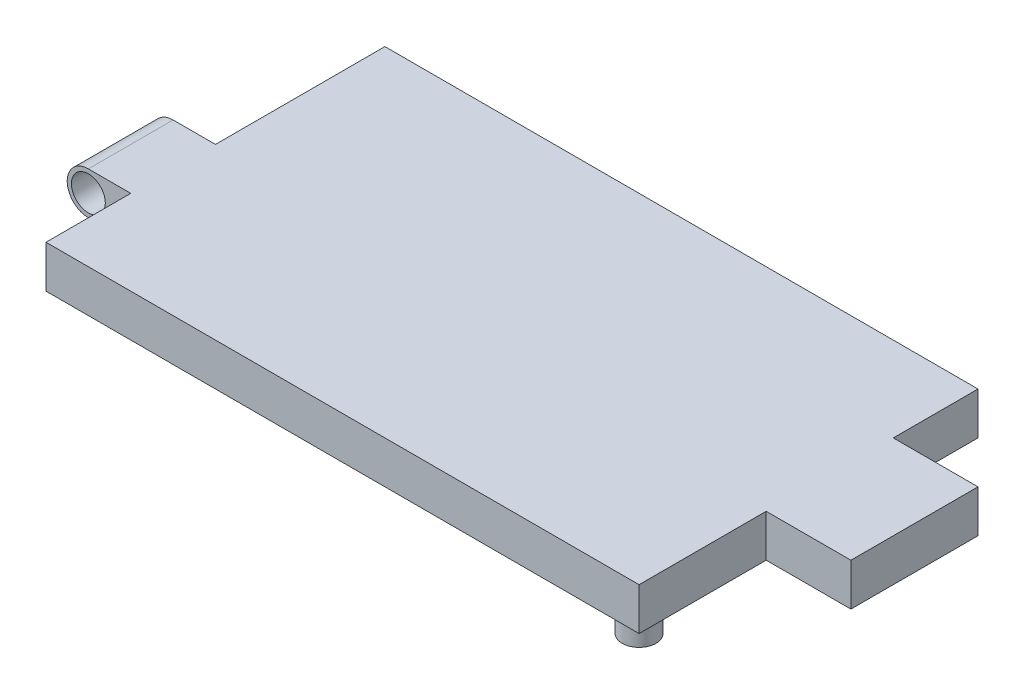
SolidWorks part; units mm, degrees
ref_plane "Plan de face" through (0, 0, 0) normal (0, 0, 1) x (1, 0, 0)
ref_plane "Plan de dessus" through (0, 0, 0) normal (0, 1, 0) x (1, 0, 0)
ref_plane "Plan de droite" through (0, 0, 0) normal (1, 0, 0) x (0, 0, -1)
sketch "Esquisse1" plane through (0, 0, 0) normal (0, 0, 1) x (1, 0, 0)
  line L0 (-80, 33.1442) -> (-80, -29.1403) construction
  line L5 (82.5, 15) -> (-82.5, -15) construction
  line L6 (82.5, -15) -> (-82.5, 15) construction
  line L7 (-88.7967, 0) -> (66.0295, 0) construction
  line L8 (-80, 2.5) -> (0, 2.5)
  line L9 (0, 2.5) -> (0, -2.5)
  line L10 (0, -2.5) -> (-80, -2.5)
  circle A0 centre (-80, 0) radius 2
  arc A1 (-80, 2.5) -> (-80, -2.5) centre (-80, 0) ccw
  point P0 (0, 0)
  dimension "D4" = 4
  dimension "D1" = 165
  dimension "D2" = 30
  dimension "D3" = 80
extrude "BASE" add sketch "Esquisse1" along normal blind 5 and the other way blind 5
sketch "Esquisse2" plane through (0, 0, 5) normal (0, 0, 1) x (1, 0, 0)
  line L0 (-75, 2.5) -> (-75, -2.5)
  line L1 (0, 2.5) -> (-80, 2.5) construction
  line L2 (-80, -2.5) -> (0, -2.5) construction
  line L3 (-75, -2.5) -> (0, -2.5)
  line L4 (0, -2.5) -> (0, 2.5)
  line L5 (0, 2.5) -> (-75, 2.5)
  dimension "D1" = 75
extrude "BOSS GRAND" add sketch "Esquisse2" along normal blind 10
sketch "Esquisse3" plane through (0, 0, -5) normal (0, 0, -1) x (-1, 0, 0)
  line L0 (0, 2.5) -> (0, -2.5)
  line L1 (0, -2.5) -> (75, -2.5)
  line L2 (80, -2.5) -> (0, -2.5) construction
  line L3 (75, -2.5) -> (75, 2.5)
  line L4 (0, 2.5) -> (80, 2.5) construction
  line L5 (75, 2.5) -> (0, 2.5)
  dimension "D1" = 75
extrude "BOSS PETIT" add sketch "Esquisse3" along normal blind 10
sketch "Esquisse4" plane through (0, 2.5, 0) normal (0, 1, 0) x (1, 0, 0)
  line L0 (0, 15) -> (5, 15)
  line L1 (5, 15) -> (5, 0)
  line L2 (5, 0) -> (0, 0)
  line L4 (0, 15) -> (0, 0)
  dimension "D1" = 5
extrude "BOSS BLOQUER" add sketch "Esquisse4" against normal blind 5
sketch "Esquisse5" plane through (0, 2.5, 0) normal (0, 1, 0) x (1, 0, 0)
  line L0 (0, 0) -> (-5, 0)
  line L1 (-5, 0) -> (-5, -15)
  line L2 (0, -15) -> (-75, -15) construction
  line L3 (-5, -15) -> (0, -15)
  line L4 (0, -15) -> (0, 0)
  dimension "D1" = 5
extrude "VIDE BLOQUER" cut sketch "Esquisse5" against normal blind 5
sketch "Esquisse6" plane through (0, 0, -15) normal (0, 0, -1) x (-1, 0, 0)
  line L1 (5, -2.5) -> (75, -2.5)
  line L2 (5, -2.5) -> (5, 2.5)
  line L3 (5, 2.5) -> (75, 2.5)
  line L4 (75, -2.5) -> (75, 2.5)
  dimension "D1" = 70
extrude "BOSS BAS" add sketch "Esquisse6" along normal blind 10
sketch "Esquisse8" plane through (0, -2.5, 0) normal (0, -1, 0) x (1, 0, 0)
  line L0 (-10, 21.5961) -> (-10, -32.1705) construction
  line L1 (-75, 15) -> (-5, 15) construction
  circle A0 centre (-10, 10) radius 2
  dimension "D3" = 4
  dimension "D1" = 10
  dimension "D2" = 5
extrude "ATTACHE CORDE" add sketch "Esquisse8" along normal blind 5
